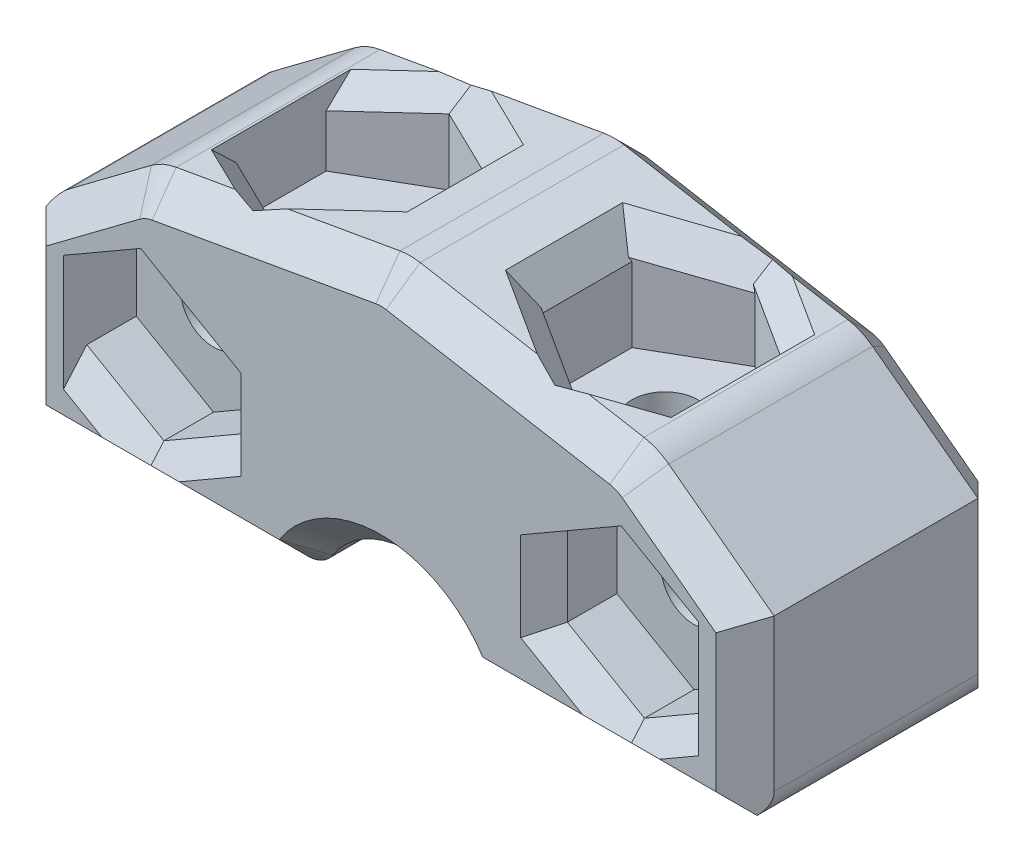
SolidWorks part; units mm, degrees
ref_plane "Front Plane" through (0, 0, 0) normal (0, 0, 1) x (1, 0, 0)
ref_plane "Top Plane" through (0, 0, 0) normal (0, 1, 0) x (1, 0, 0)
ref_plane "Right Plane" through (0, 0, 0) normal (1, 0, 0) x (0, 0, -1)
sketch "Sketch1" plane through (0, 0, 0) normal (0, 0, 1) x (1, 0, 0)
  line L0 (-3.175, 0) -> (-12.5, 0)
  line L1 (-12.5, 0) -> (-12.5, 12)
  line L2 (-12.5, 12) -> (12.5, 12)
  line L3 (0, 12) -> (0, 3.3) construction
  line L4 (12.5, 0) -> (12.5, 12)
  line L5 (3.175, 0) -> (12.5, 0)
  arc A0 (3.175, 0) -> (-3.175, 0) centre (0, 0) ccw
  dimension "D1" = 6.35
  dimension "D2" = 25
  dimension "D3" = 12
extrude "Boss-Extrude1" add sketch "Sketch1" along normal blind 9
sketch "Sketch2" plane through (0, 0, 9) normal (0, 0, 1) x (1, 0, 0)
  line L0 (0, 12) -> (-8.5, 10.5)
  line L1 (12.5, 12) -> (-12.5, 12) construction
  line L2 (-8.5, 10.5) -> (-12.5, 7.5044)
  line L3 (-12.5, 12) -> (-12.5, 0) construction
  line L4 (-12.5, 7.5044) -> (-12.5, 12)
  line L5 (-12.5, 12) -> (12.5, 12)
  line L6 (0, 8.1862) -> (0, -3.9101) construction
  line L7 (12.5, 7.5044) -> (12.5, 12)
  line L8 (8.5, 10.5) -> (12.5, 7.5044)
  line L9 (0, 12) -> (8.5, 10.5)
  line L10 (-12.5, 0) -> (-3.175, 0) construction
  line M8 (12.5, 0) -> (12.5, 12)
  line M9 (12.5, 12) -> (-12.5, 12)
  line M10 (-12.5, 12) -> (-12.5, 0)
  dimension "D1" = 10.5
  dimension "D2" = 17
  dimension "D3" = 4.4956
extrude "Cut-Extrude1" cut sketch "Sketch2" against normal through all both and the other way through all contours L2 L0 M9 M10 | L9 L8 M9 M8 region at (-9.0398, 10.7664, 9) region at (9.0398, 10.7664, 9)
chamfer "Chamfer1" distance 1 angle 45 4 edges at (-12.5, 3.7522, 0) (12.5, 3.7522, 0) (12.5, 3.7522, 9) (-12.5, 3.7522, 9)
sketch "Sketch8" plane through (0, 0, 0) normal (0, 0, -1) x (-1, 0, 0)
  line L0 (12.5, 7.5044) -> (12.5, 0) construction
  line L1 (-12.5, 0) -> (12.5, 0)
  line L2 (-12.5, 0) -> (-12.5, 1.2804)
  line L3 (-12.5, 1.2804) -> (12.5, 1.2804)
  line L4 (12.5, 0) -> (12.5, 1.2804)
extrude "Cut-Extrude6" cut sketch "Sketch8" against normal through all both and the other way through all
fillet "Fillet3" radius 1 4 edges at (-12.5, 1.2804, 4.5) (-2.9054, 1.2804, 4.5) (12.5, 1.2804, 4.5) (2.9054, 1.2804, 4.5)
sketch "Sketch4" plane through (0, 1.2804, 0) normal (0, -1, 0) x (1, 0, 0)
  line L0 (0, 9) -> (0, 0) construction
  line L1 (-5.25, 4.5) -> (5.25, 4.5) construction
  line L2 (2.6595, 9) -> (-2.6595, 9) construction
  circle A0 centre (-5.25, 4.5) radius 1.125
  circle A1 centre (5.25, 4.5) radius 1.125
  point P8 (0, 4.5)
  point P17 (0, 4.5)
  dimension "D2" = 2.25
  dimension "D1" = 10.5
extrude "Cut-Extrude2" cut sketch "Sketch4" against normal through all
sketch "Sketch5" plane through (0, 0, 0) normal (0, 1, 0) x (1, 0, 0)
  line L1 (-5.25, -7.5888) -> (-2.575, -6.0444)
  line L2 (-2.575, -6.0444) -> (-2.575, -2.9556)
  line L3 (-2.575, -2.9556) -> (-5.25, -1.4112)
  line L4 (-5.25, -1.4112) -> (-7.925, -2.9556)
  line L5 (-7.925, -2.9556) -> (-7.925, -6.0444)
  line L6 (-7.925, -6.0444) -> (-5.25, -7.5888)
  line L7 (5.25, -7.5888) -> (7.925, -6.0444)
  line L8 (7.925, -6.0444) -> (7.925, -2.9556)
  line L9 (7.925, -2.9556) -> (5.25, -1.4112)
  line L10 (5.25, -1.4112) -> (2.575, -2.9556)
  line L11 (2.575, -2.9556) -> (2.575, -6.0444)
  line L12 (2.575, -6.0444) -> (5.25, -7.5888)
  circle A2 centre (-5.25, -4.5) radius 2.675 construction
  circle A3 centre (5.25, -4.5) radius 2.675 construction
  dimension "D1" = 5.35
extrude "Cut-Extrude3" cut sketch "Sketch5" along normal blind 8 from offset 8
fillet "Fillet2" radius 2 4 edges at (8.5, 10.5, 4.5) (-8.5, 10.5, 4.5) (0, 12, 4.5) (-12.5, 7.5044, 4.5)
chamfer "Chamfer2" distance 1 angle 45 12 edges at (0, 3.175, 9) (10.1908, 9.2337, 9) (8.4777, 10.4486, 9) (4.189, 11.2608, 9) (-10.1908, 9.2337, 9) (0, 11.9691, 9) (-8.4777, 10.4486, 9) (-4.189, 11.2608, 9) (-7.4986, 1.2804, 9) (7.4986, 1.2804, 9) (-3.0208, 1.4012, 9) (3.0208, 1.4012, 9)
sketch "Sketch6" plane through (0, 0, 9) normal (0, 0, 1) x (1, 0, 0)
  line L0 (-8.25, 5.5) -> (8.25, 5.5) construction
  circle A0 centre (-8.25, 5.5) radius 1.125
  circle A1 centre (8.25, 5.5) radius 1.125
  point P4 (0, 5.5)
  dimension "D2" = 2.25
  dimension "D1" = 16.5
  dimension "D3" = 5.5
extrude "Cut-Extrude4" cut sketch "Sketch6" against normal through all
sketch "Sketch7" plane through (0, 0, 9) normal (0, 0, 1) x (1, 0, 0)
  line L1 (-8.25, 2.44) -> (-5.6, 3.97)
  line L2 (-5.6, 3.97) -> (-5.6, 7.03)
  line L3 (-5.6, 7.03) -> (-8.25, 8.56)
  line L4 (-8.25, 8.56) -> (-10.9, 7.03)
  line L5 (-10.9, 7.03) -> (-10.9, 3.97)
  line L6 (-10.9, 3.97) -> (-8.25, 2.44)
  line L7 (8.25, 2.44) -> (10.9, 3.97)
  line L8 (10.9, 3.97) -> (10.9, 7.03)
  line L9 (10.9, 7.03) -> (8.25, 8.56)
  line L10 (8.25, 8.56) -> (5.6, 7.03)
  line L11 (5.6, 7.03) -> (5.6, 3.97)
  line L12 (5.6, 3.97) -> (8.25, 2.44)
  circle A0 centre (-8.25, 5.5) radius 2.65 construction
  circle A1 centre (8.25, 5.5) radius 2.65 construction
  dimension "D1" = 5.3
extrude "Cut-Extrude5" cut sketch "Sketch7" against normal blind 2.5
chamfer "Chamfer3" distance 0.8 angle 45 16 edges at (5.6, 5.5, 9) (9.575, 3.205, 9) (6.925, 3.205, 9) (-5.6, 5.5, 9) (-9.575, 3.205, 9) (-6.925, 3.205, 9) (3.9125, 11.3096, 6.8166) (6.5875, 10.8375, 6.8166) (6.5875, 10.8375, 2.1834) (2.575, 11.5456, 4.5) (3.9125, 11.3096, 2.1834) (-6.5875, 10.8375, 6.8166) (-3.9125, 11.3096, 6.8166) (-2.575, 11.5456, 4.5) (-3.9125, 11.3096, 2.1834) (-6.5875, 10.8375, 2.1834) first distance on face at (-8.25, 5.5, 9) first distance on face at (4.189, 11.2608, 4) first distance on face at (-6.5875, 9.4187, 6.8166) first distance on face at (-3.9125, 9.6548, 6.8166) first distance on face at (-2.575, 9.7728, 4.5) first distance on face at (-3.9125, 9.6548, 2.1834) first distance on face at (-6.5875, 9.4187, 2.1834)
chamfer "Chamfer4" distance 1 angle 45 12 edges at (10.1908, 9.2337, 0) (8.4777, 10.4486, 0) (4.189, 11.2608, 0) (-10.1908, 9.2337, 0) (0, 11.9691, 0) (-8.4777, 10.4486, 0) (-4.189, 11.2608, 0) (7.4986, 1.2804, 0) (3.0208, 1.4012, 0) (0, 3.175, 0) (-3.0208, 1.4012, 0) (-7.4986, 1.2804, 0)
chamfer "Chamfer5" distance 1 angle 45 2 edges at (9.375, 5.5, 0) (-7.125, 5.5, 0)
